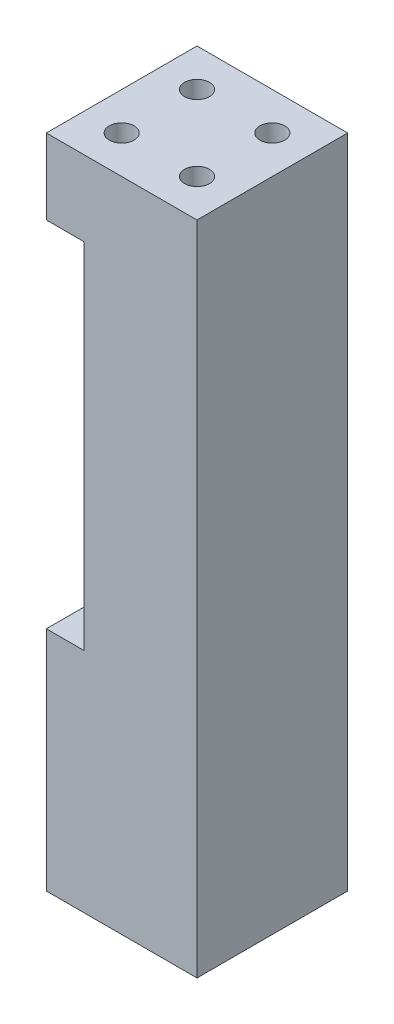
SolidWorks part; units mm, degrees
ref_plane "前视基准面" through (0, 0, 0) normal (0, 0, 1) x (1, 0, 0)
ref_plane "上视基准面" through (0, 0, 0) normal (0, 1, 0) x (1, 0, 0)
ref_plane "右视基准面" through (0, 0, 0) normal (1, 0, 0) x (0, 0, -1)
sketch "草图1" plane through (0, 0, 0) normal (0, 0, 1) x (1, 0, 0)
  line L0 (-20, 30.15) -> (-15, 30.15)
  line L1 (-15, 30.15) -> (-15, 77.15)
  line L2 (-15, 77.15) -> (-20, 77.15)
  line L3 (0, 87.15) -> (-20, 87.15)
  line L4 (0, 0) -> (0, 87.15)
  line L5 (-20, 0) -> (0, 0)
  line L6 (-20, 30.15) -> (-20, 0)
  line L7 (-20, 87.15) -> (-20, 77.15)
extrude "凸台-拉伸1" add sketch "草图1" along normal blind 20
hole_wizard "M4 螺纹孔1" positions "草图2" profile "草图3" tap size "M4" standard "ISO"
sketch "草图2" plane through (0, 87.15, 0) normal (0, 1, 0) x (1, 0, 0)
  line L0 (-10, 0) -> (-10, -20) construction
  line L1 (0, 0) -> (-20, 0) construction
  line L2 (0, -20) -> (-20, -20) construction
  line L3 (-10, -20) -> (-10, -10) construction
  line L4 (-10, -10) -> (0, -10) construction
  line L5 (0, -20) -> (0, 0) construction
  point P0 (-15, -5)
  point P2 (-5, -5)
  point P4 (-15, -15)
  point P6 (-5, -15)
  point P22 (0, 0)
  point P23 (0, 0)
  point P28 (-14.4725, -11.1542)
  dimension "D1" = 10
  dimension "D2" = 10
sketch "草图3" plane through (-15, 87.15, 5) normal (1, 0, 0) x (0, 0, 1)
  line L0 (0, 0) -> (0, 11.0914)
  line L1 (0, 11.0914) -> (1.65, 10.1)
  line L2 (1.65, 10.1) -> (1.65, 0)
  line L5 (1.65, 0) -> (0, 0)
  line L10 (0, 11.0914) -> (-1.65, 10.1) construction
  line L11 (0, -6.35) -> (0, 107.95) construction
  dimension "螺纹孔钻头直径" = 3.3
  dimension "螺纹孔钻头深度" = 10.1
  dimension "导头角度" = 118
cosmetic thread "孔螺蚊线1" parameters "D1"=8, "D2"=4
cosmetic thread "孔螺蚊线2" parameters "D1"=8, "D2"=4
cosmetic thread "孔螺蚊线3" parameters "D1"=8, "D2"=4
cosmetic thread "孔螺蚊线4" parameters "D1"=8, "D2"=4
ref_plane "基准面2" through (0, 43.575, 0) normal (0, 1, 0) x (1, 0, 0)
mirror "镜向1" about plane through (0, 43.575, 0) normal (0, 1, 0) of "M4 螺纹孔1"
